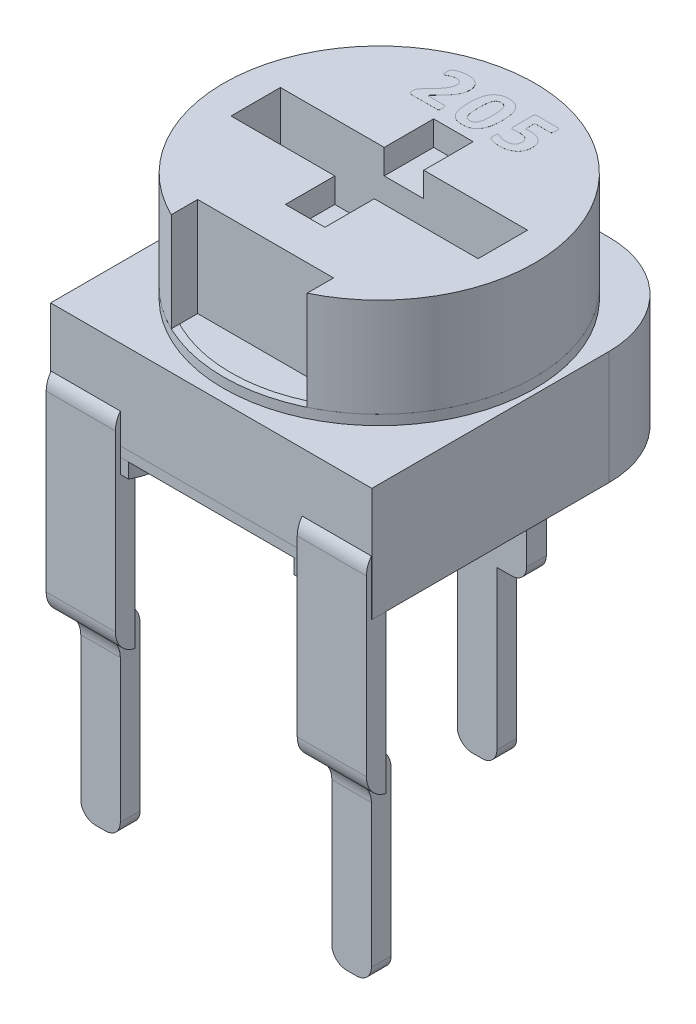
SolidWorks part; units mm, degrees
material "ABS"
ref_plane "Front Plane" through (0, 0, 0) normal (0, 0, 1) x (1, 0, 0)
ref_plane "Top Plane" through (0, 0, 0) normal (0, 1, 0) x (1, 0, 0)
ref_plane "Right Plane" through (0, 0, 0) normal (1, 0, 0) x (0, 0, -1)
sketch "Sketch1" plane through (0, 0, 0) normal (0, 1, 0) x (1, 0, 0)
  line L0 (0, 3.15) -> (0, -3.15) construction
  line L1 (0, 3.15) -> (0, 3.4) construction
  line L2 (0, -3.15) -> (0, -3.4) construction
  line L3 (-3.15, 0) -> (3.15, 0) construction
  line L4 (3.15, 0) -> (3.25, 0) construction
  line L5 (-3.15, 0) -> (-3.25, 0) construction
  line L6 (-3.25, -3.4) -> (3.25, -3.4)
  line L7 (-3.25, -3.4) -> (-3.25, 3.4)
  line L8 (-3.25, 3.4) -> (3.25, 3.4)
  line L9 (3.25, 3.4) -> (3.25, -3.4)
  circle A0 centre (0, 0) radius 3.15 construction
  dimension "D1" = 6.3
  dimension "D2" = 6.8
  dimension "D3" = 6.5
extrude "Boss-Extrude1" add sketch "Sketch1" along normal blind 2.3
sketch "Sketch2" plane through (0, 2.3, 0) normal (0, 1, 0) x (1, 0, 0)
  circle A0 centre (0, 0) radius 3.15 construction
  circle A1 centre (0, 0) radius 3.15
extrude "Boss-Extrude2" add sketch "Sketch2" along normal blind 0.2
fillet "Fillet1" radius 2 2 edges at (3.25, 1.15, -3.4) (-3.25, 1.15, -3.4)
sketch "Sketch3" plane through (0, 0, 0) normal (0, -1, 0) x (1, 0, 0)
  line L0 (0, 0) -> (0, -2.5) construction
  line L1 (-1.75, -2.5) -> (1.75, -2.5)
  line L6 (-2.25, -2) -> (-2.25, 2)
  line L7 (2.25, -2) -> (2.25, 2)
  line L8 (-2.25, 2) -> (-3, 2)
  line L9 (-3, 2) -> (-3, 3.4)
  line L10 (-3.25, 3.4) -> (3.25, 3.4) construction
  line L11 (2.25, 2) -> (3, 2)
  line L12 (3, 2) -> (3, 3.4)
  line L13 (3, 3.4) -> (-3, 3.4)
  line L14 (0, 0) -> (0, 3.4) construction
  arc A0 (-1.75, -2.5) -> (-2.25, -2) centre (-1.75, -2) cw
  arc A1 (1.75, -2.5) -> (2.25, -2) centre (1.75, -2) ccw
  point P20 (2.25, -2.5)
  dimension "D6" = 0.5
  dimension "D1" = 4.5
  dimension "D2" = 2.5
  dimension "D3" = 4.5
  dimension "D4" = 1.4
  dimension "D5" = 6
extrude "Cut-Extrude1" cut sketch "Sketch3" against normal blind 0.5
sketch "Sketch4" plane through (0, 0.5, 0) normal (0, -1, 0) x (1, 0, 0)
  line L8 (-3, 2) -> (-2.25, 2)
  line L9 (-2.25, 2) -> (-2.25, -2)
  line L10 (-1.75, -2.5) -> (1.75, -2.5)
  line L11 (2.25, -2) -> (2.25, 2)
  line L12 (2.25, 2) -> (3, 2)
  line L13 (3, 2) -> (3, 3.4)
  line L14 (3, 3.4) -> (-3, 3.4)
  line L15 (-3, 3.4) -> (-3, 2)
  line L16 (-3, 2) -> (-2.25, 2)
  line L17 (-2.25, 2) -> (-2.25, -2)
  line L18 (-1.75, -2.5) -> (1.75, -2.5)
  line L19 (2.25, -2) -> (2.25, 2)
  line L20 (2.25, 2) -> (3, 2)
  line L21 (3, 2) -> (3, 3.4)
  line L22 (3, 3.4) -> (-3, 3.4)
  line L23 (-3, 3.4) -> (-3, 2)
  arc A2 (-2.25, -2) -> (-1.75, -2.5) centre (-1.75, -2) ccw
  arc A3 (1.75, -2.5) -> (2.25, -2) centre (1.75, -2) ccw
  arc A4 (-2.25, -2) -> (-1.75, -2.5) centre (-1.75, -2) ccw
  arc A5 (1.75, -2.5) -> (2.25, -2) centre (1.75, -2) ccw
  dimension "D1" = 0
extrude "Boss-Extrude3" add sketch "Sketch4" along normal blind 0.2 separate body
sketch "Sketch5" plane through (0, 0.3, 0) normal (0, -1, 0) x (1, 0, 0)
  line L0 (0, 3.4) -> (0, 2.9) construction
  line L1 (3, 3.4) -> (-3, 3.4) construction
  line L2 (0, 2.9) -> (0, -2.18) construction
  line L3 (-2.54, 2.9) -> (2.54, 2.9) construction
  circle A0 centre (2.54, 2.9) radius 1
  circle A1 centre (-2.54, 2.9) radius 1
  circle A2 centre (0, -2.18) radius 1
  dimension "D2" = 5.08
  dimension "D4" = 2
  dimension "D1" = 0.5
  dimension "D3" = 5.08
extrude "Boss-Extrude4" add sketch "Sketch5" along normal up to surface (0.3 mm away) up to face at (0, 0, 0.1228)
sketch "Sketch6" plane through (0, 0.3, 0) normal (0, 1, 0) x (1, 0, 0)
  line L0 (-3.25, -3.4) -> (-3.25, -1)
  line L1 (-3.25, 1.4) -> (-3.25, -3.4) construction
  line L2 (-3.25, -1) -> (-4.35, -1)
  line L3 (-4.35, -1) -> (-4.35, -4.5)
  line L4 (-4.35, -4.5) -> (4.35, -4.5)
  line L5 (4.35, -4.5) -> (4.35, -1)
  line L6 (4.35, -1) -> (3.25, -1)
  line L7 (3.25, -3.4) -> (3.25, 1.4) construction
  line L8 (-3.25, -3.4) -> (3.25, -3.4)
  line L9 (3.25, -3.4) -> (3.25, -1)
  line L10 (0, 0) -> (0, -3.4) construction
  line L11 (0, -3.4) -> (0, -4.5) construction
  dimension "D1" = 3.5
extrude "Cut-Extrude2" cut sketch "Sketch6" against normal up to surface (0.3 mm away) up to face at (0, 0, -0.817)
sketch "Sketch8" plane through (0, 0.3, 0) normal (0, -1, 0) x (1, 0, 0)
  line L1 (-0.4, -1.98) -> (0.4, -1.98)
  line L2 (-0.4, -1.98) -> (-0.4, -2.38)
  line L3 (-0.4, -2.38) -> (0.4, -2.38)
  line L4 (0.4, -1.98) -> (0.4, -2.38)
  line L5 (-0.4, -1.98) -> (0.4, -2.38) construction
  line L6 (-0.4, -2.38) -> (0.4, -1.98) construction
  line L7 (-2.94, 3.1) -> (-2.14, 3.1)
  line L8 (-2.94, 3.1) -> (-2.94, 2.7)
  line L9 (-2.94, 2.7) -> (-2.14, 2.7)
  line L10 (-2.14, 3.1) -> (-2.14, 2.7)
  line L11 (-2.94, 3.1) -> (-2.14, 2.7) construction
  line L12 (-2.94, 2.7) -> (-2.14, 3.1) construction
  line L13 (2.94, 3.1) -> (2.14, 3.1)
  line L14 (2.94, 3.1) -> (2.94, 2.7)
  line L15 (2.94, 2.7) -> (2.14, 2.7)
  line L16 (2.14, 3.1) -> (2.14, 2.7)
  line L17 (2.94, 3.1) -> (2.14, 2.7) construction
  line L18 (2.94, 2.7) -> (2.14, 3.1) construction
  point P0 (0, -2.18)
  point P5 (-2.54, 2.9)
  point P11 (2.54, 2.9)
  dimension "D1" = 0.4
  dimension "D2" = 0.8
extrude "Boss-Extrude5" add sketch "Sketch8" along normal blind 7
sketch "Sketch9" plane through (0, 0.3, 0) normal (0, -1, 0) x (1, 0, 0)
  line L4 (0, -1.98) -> (0, -2.38) construction
  line L5 (0.4, -1.98) -> (-0.4, -1.98) construction
  line L6 (-0.4, -2.38) -> (0.4, -2.38) construction
  line L8 (-1, -1.98) -> (1, -1.98)
  line L9 (-1, -1.98) -> (-1, -2.38)
  line L10 (-1, -2.38) -> (1, -2.38)
  line L11 (1, -1.98) -> (1, -2.38)
  line L12 (-1, -1.98) -> (1, -2.38) construction
  line L13 (-1, -2.38) -> (1, -1.98) construction
  point P14 (0, -2.18)
  dimension "D1" = 2
extrude "Boss-Extrude6" add sketch "Sketch9" along normal blind 3.5
sketch "Sketch10" plane through (0, 0.3, 0) normal (0, -1, 0) x (1, 0, 0)
  line L0 (-2.54, 3.1) -> (-2.54, 3.5) construction
  line L1 (-2.14, 3.1) -> (-2.94, 3.1) construction
  line L2 (2.54, 3.1) -> (2.54, 3.5) construction
  line L3 (2.94, 3.1) -> (2.14, 3.1) construction
  line L4 (-2.94, 3.1) -> (-2.94, 2.7) construction
  line L5 (-3.24, 3.5) -> (-1.84, 3.5)
  line L6 (-3.24, 3.5) -> (-3.24, 3.1)
  line L7 (-3.24, 3.1) -> (-1.84, 3.1)
  line L8 (-1.84, 3.5) -> (-1.84, 3.1)
  line L10 (1.84, 3.5) -> (3.24, 3.5)
  line L11 (1.84, 3.5) -> (1.84, 3.1)
  line L12 (1.84, 3.1) -> (3.24, 3.1)
  line L13 (3.24, 3.5) -> (3.24, 3.1)
  dimension "D1" = 1.4
extrude "Boss-Extrude7" add sketch "Sketch10" along normal blind 3.5 and the other way blind 1
fillet "Fillet2" radius 0.5 2 edges at (2.54, 1.3, 3.5) (-2.54, 1.3, 3.5)
sketch "Sketch11" plane through (0, 0, 0) normal (1, 0, 0) x (0, 0, -1)
  line L0 (-3.4, 0) -> (1.4, 0) construction
  line L1 (-3.1, -2.8) -> (-2.7, -2.8)
  line L2 (-3.1, -2.8) -> (-3.1, 0)
  line L3 (-3.1, 0) -> (-2.7, 0)
  line L4 (-2.7, -2.8) -> (-2.7, 0)
  line L5 (-2.7, -6.7) -> (-2.7, 0.3) construction
  line L6 (-3.1, -2.8) -> (-3.1, -3.2) construction
extrude "Cut-Extrude3" cut sketch "Sketch11" against normal through all both and the other way through all
fillet "Fillet3" radius 0.5 4 edges at (-2.54, -2.8, 3.1) (2.54, -2.8, 3.1) (-2.54, -3.2, 3.5) (2.54, -3.2, 3.5)
fillet "Fillet4" radius 0.5 4 edges at (2.54, -2.8, 2.7) (-2.54, -2.8, 2.7) (2.54, -3.2, 3.1) (-2.54, -3.2, 3.1)
fillet "Fillet5" radius 0.3 12 edges at (-1, -3.2, -2.18) (1, -3.2, -2.18) (-0.4, -6.7, -2.18) (0.4, -6.7, -2.18) (2.14, -6.7, 2.9) (2.94, -6.7, 2.9) (-2.94, -6.7, 2.9) (-2.14, -6.7, 2.9) (-2.14, -2.7551, 3.1) (-2.94, -2.7551, 3.1) (2.14, -2.7551, 3.1) (2.94, -2.7551, 3.1)
sketch "Sketch12" plane through (0, 0.3, 0) normal (0, -1, 0) x (1, 0, 0)
  circle A0 centre (0, 0) radius 2
  circle A1 centre (0, 0) radius 1.5
  dimension "D1" = 4
  dimension "D2" = 3
extrude "Boss-Extrude8" add sketch "Sketch12" along normal blind 0.15
sketch "Sketch15" plane through (0, 2.5, 0) normal (0, 1, 0) x (1, 0, 0)
  circle A0 centre (0, 0) radius 3
  dimension "D1" = 6
extrude "Cut-Extrude4" cut sketch "Sketch15" against normal blind 0.5
sketch "Sketch14" plane through (0, 2.5, 0) normal (0, 1, 0) x (1, 0, 0)
  circle A1 centre (0, 0) radius 3.15
  circle A2 centre (0, 0) radius 3.15
  dimension "D1" = 0
extrude "Boss-Extrude9" add sketch "Sketch14" along normal blind 2 separate body
sketch "Set Angle of Knob" plane through (0, 4.5, 0) normal (0, 1, 0) x (1, 0, 0)
  line L0 (0, 0) -> (0, -3.15) construction
  line L1 (-2.5, 0) -> (2.5, 0) construction
  line L2 (-2.5, 0.5) -> (-2.5, -0.5)
  line L3 (2.5, 0.5) -> (2.5, -0.5)
  line L4 (-2.5, 0.5) -> (-0.4, 0.5)
  line L5 (-2.5, -0.5) -> (-0.4, -0.5)
  line L6 (0, 0) -> (0, -1.5) construction
  line L7 (0, 0) -> (0, 1.5) construction
  line L8 (0, 1.5) -> (0, 3.15) construction
  line L9 (0.4, 1.5) -> (-0.4, 1.5)
  line L10 (0.4, 1.5) -> (0.4, 0.5)
  line L11 (-0.4, 1.5) -> (-0.4, 0.5)
  line L12 (0.4, 0.5) -> (2.5, 0.5)
  line L13 (-0.4, -1.5) -> (0.4, -1.5)
  line L14 (-0.4, -1.5) -> (-0.4, -0.5)
  line L15 (0.4, -1.5) -> (0.4, -0.5)
  line L16 (0.4, -0.5) -> (2.5, -0.5)
  line L17 (0, -1.5) -> (0, -2.3) construction
  line L18 (-1.375, -2.3) -> (1.375, -2.3)
  line L19 (-1.375, -2.3) -> (-1.375, -3.8)
  line L20 (1.375, -2.3) -> (1.375, -3.8)
  line L21 (-1.375, -3.8) -> (1.375, -3.8)
  line L22 (-1, 0.25) -> (1, 0.25) construction
  line L23 (-1, 0.25) -> (-1, -0.25) construction
  line L24 (-1, -0.25) -> (1, -0.25) construction
  line L25 (1, -0.25) -> (1, 0.25) construction
  circle A0 centre (0, 0) radius 3.15 construction
  circle A1 centre (0, 0) radius 3.15 construction
  point P32 (0, 0.25)
  dimension "D1" = 1
  dimension "D2" = 0.8
  dimension "D3" = 1.5
  dimension "D4" = 5
  dimension "D5" = 90
  dimension "D6" = 2.75
  dimension "D7" = 1.5
  dimension "D8" = 1.8
  dimension "D9" = 0.25
  dimension "D10" = 0.25
  dimension "D11" = 2
extrude "TURN KNOB" cut sketch "Set Angle of Knob" against normal blind 2.3
sketch "Sketch17" plane through (0, 2, 0) normal (0, 1, 0) x (1, 0, 0)
  line L0 (-0.4, -1.5) -> (0.4, -1.5)
  line L1 (0.4, -1.5) -> (0.4, -0.5)
  line L2 (0.4, 1.5) -> (-0.4, 1.5)
  line L3 (-0.4, 1.5) -> (-0.4, 0.5)
  line L4 (-0.4, 0.5) -> (0.4, 0.5)
  line L5 (-0.4, -0.5) -> (0.4, -0.5)
  line L6 (-0.4, -0.5) -> (-0.4, -1.5)
  line L7 (0.4, 0.5) -> (0.4, 1.5)
extrude "Boss-Extrude10" add sketch "Sketch17" along normal blind 2
sketch "Sketch20" plane through (0, 2, 0) normal (0, 1, 0) x (1, 0, 0)
  line L0 (-1, 0.25) -> (1, 0.25) construction
  line L1 (-1, 0.25) -> (1, 0.25)
  line L2 (-1, -0.25) -> (1, -0.25) construction
  line L3 (-1, -0.25) -> (1, -0.25)
  line L4 (-1, 0.25) -> (-1, -0.25) construction
  line L5 (-1, 0.25) -> (-1, -0.25)
  line L6 (1, -0.25) -> (1, 0.25) construction
  line L7 (1, -0.25) -> (1, 0.25)
extrude "Cut-Extrude6" cut sketch "Sketch20" against normal blind 0.5
fillet "Fillet6" radius 0.2 2 edges at (1, 2, 0) (-1, 2, 0)
sketch "See Code in Properties" plane through (0, 4.5, 0) normal (0, 1, 0) x (1, 0, 0)
  line L0 (0, 1.5) -> (0, 1.7) construction
  line L1 (0.4, 1.5) -> (-0.4, 1.5) construction
  line L2 (0, 1.5) -> (0, 3.15) construction
  line L3 (-1.5, 1.7) -> (1.5, 1.7) construction
  text T0 "205" font "Calibri" height 0.9
  dimension "D1" = 0.2
  dimension "D2" = 3
extrude "Code Number" add sketch "See Code in Properties" along normal blind 0.001
